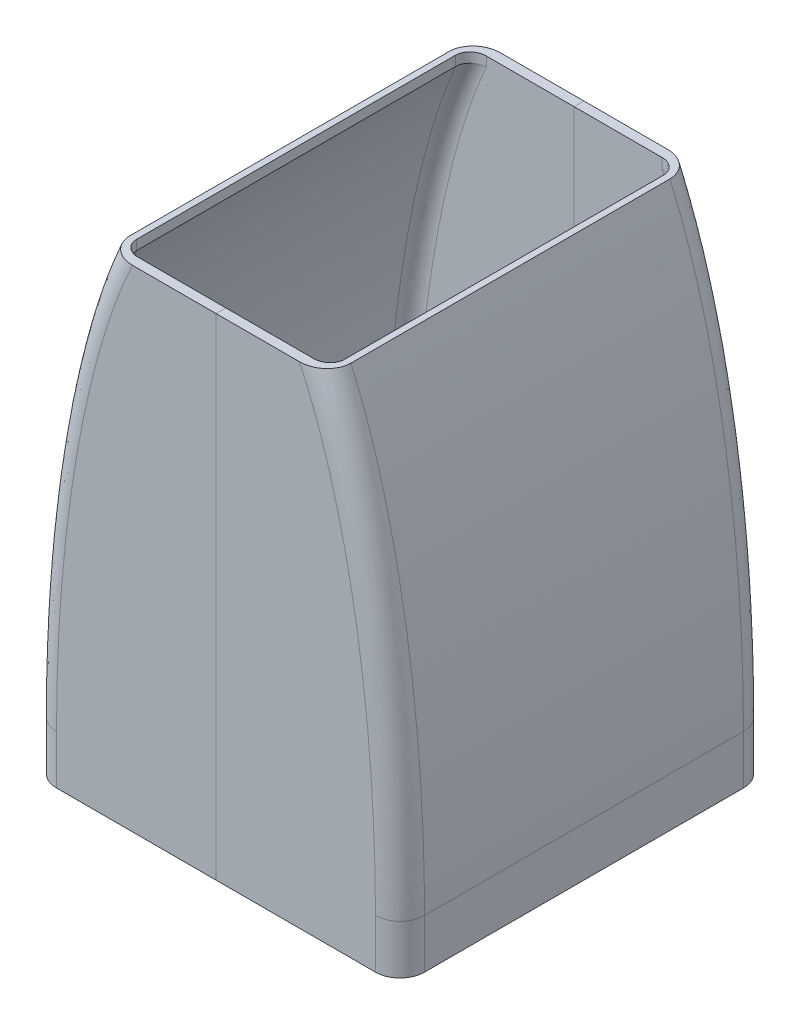
SolidWorks part; units mm, degrees
ref_plane "Front Plane" through (0, 0, 0) normal (0, 0, 1) x (1, 0, 0)
ref_plane "Top Plane" through (0, 0, 0) normal (0, 1, 0) x (1, 0, 0)
ref_plane "Right Plane" through (0, 0, 0) normal (1, 0, 0) x (0, 0, -1)
sketch "Sketch1" plane through (0, 0, 0) normal (0, 1, 0) x (1, 0, 0)
  line L1 (-37.5, 37.5) -> (37.5, 37.5)
  line L2 (-37.5, 37.5) -> (-37.5, -37.5)
  line L3 (-37.5, -37.5) -> (37.5, -37.5)
  line L4 (37.5, 37.5) -> (37.5, -37.5)
  line L5 (-37.5, 37.5) -> (37.5, -37.5) construction
  line L6 (-37.5, -37.5) -> (37.5, 37.5) construction
  point P0 (0, 0)
  dimension "D1" = 75
  dimension "D2" = 75
extrude "Boss-Extrude1" add sketch "Sketch1" along normal blind 10
sketch "Sketch2" plane through (0, 0, 37.5) normal (0, 0, 1) x (1, 0, 0)
  line L0 (0, 0) -> (0, 100) construction
  line L1 (-22.5, 100) -> (22.5, 100)
  line L2 (-37.5, 10) -> (37.5, 10) construction
  line L3 (-37.5, 10) -> (37.5, 10)
  ellipse E0 centre (0, 10) end of major axis (0, 122.5) minor radius 37.5 (-22.5, 100) -> (-37.5, 10) ccw
  ellipse E1 centre (0, 10) end of major axis (0, 122.5) minor radius 37.5 (37.5, 10) -> (22.5, 100) ccw
  point P5 (0, 100)
  dimension "D1" = 100
  dimension "D2" = 45
extrude "Boss-Extrude2" add sketch "Sketch2" against normal blind 75
fillet "Fillet3" radius 5 8 edges at (37.5, 5, 37.5) (33.541, 60.3115, 37.5) (37.5, 5, -37.5) (33.541, 60.3115, -37.5) (-33.541, 60.3115, -37.5) (-37.5, 5, -37.5) (-37.5, 5, 37.5) (-33.541, 60.3115, 37.5)
shell "Shell2" thickness 2 removed face at (0, 0, 0)
sketch "Sketch5" plane through (0, 98, 0) normal (0, -1, 0) x (1, 0, 0)
  line L8 (17.9173, 35.5) -> (-17.9173, 35.5)
  line L9 (-21.1906, 32.5) -> (-21.1906, -32.5)
  line L10 (-17.9173, -35.5) -> (17.9173, -35.5)
  line L11 (21.1906, -32.5) -> (21.1906, 32.5)
  line L12 (17.9173, 35.5) -> (-17.9173, 35.5)
  line L13 (-21.1906, 32.5) -> (-21.1906, -32.5)
  line L14 (-17.9173, -35.5) -> (17.9173, -35.5)
  line L15 (21.1906, -32.5) -> (21.1906, 32.5)
  spline S8 degree 3 poles (652.9657, -3906.7243) (152.9461, -614.5841) (20.8703, 42.3054) (-18.7327, 35.412) (-18.9339, 35.3586) (-19.3197, 35.2184) (-19.505, 35.1318) (-19.8596, 34.9241) (-20.0286, 34.8026) (-20.3362, 34.5325) (-20.4773, 34.3821) (-20.7275, 34.0532) (-20.834, 33.8783) (-21.0089, 33.5075) (-21.0772, 33.3099) (-27.1431, 6.4793) (358.1812, -88.0463) (3904.516, -730.9759) knots -24.254518 -24.254518 -24.254518 -24.254518 0.125 0.125 0.25 0.25 0.375 0.375 0.5 0.5 0.625 0.625 0.75 0.75 0.875 0.875 17.555851 17.555851 17.555851 17.555851 only from (-17.9173, 35.5) to (-21.1906, 32.5)
  spline S9 degree 3 poles (1353.9761, -3785.1154) (108.5431, 47.1093) (-24.7377, -17.2738) (-21.0753, -33.3163) (-21.0082, -33.5093) (-20.8325, -33.8811) (-20.7233, -34.0592) (-20.4755, -34.3839) (-20.3358, -34.533) (-20.0253, -34.8053) (-19.857, -34.9257) (-19.5047, -35.1319) (-19.3194, -35.2187) (16.3833, -48.1691) (182.6697, 533.2285) (-3920.2957, 586.1376) knots -9.764008 -9.764008 -9.764008 -9.764008 0.125 0.125 0.25 0.25 0.375 0.375 0.5 0.5 0.625 0.625 0.75 0.75 23.581318 23.581318 23.581318 23.581318 only from (-21.1906, -32.5) to (-17.9173, -35.5)
  spline S10 degree 3 poles (-652.9657, 3906.7243) (-152.9461, 614.5841) (-20.8703, -42.3054) (18.7327, -35.412) (18.9339, -35.3586) (19.3197, -35.2184) (19.505, -35.1318) (19.8596, -34.9241) (20.0286, -34.8026) (20.3362, -34.5325) (20.4773, -34.3821) (20.7275, -34.0532) (20.834, -33.8783) (21.0089, -33.5075) (21.0772, -33.3099) (27.1431, -6.4793) (-358.1812, 88.0463) (-3904.516, 730.9759) knots -24.254518 -24.254518 -24.254518 -24.254518 0.125 0.125 0.25 0.25 0.375 0.375 0.5 0.5 0.625 0.625 0.75 0.75 0.875 0.875 17.555851 17.555851 17.555851 17.555851 only from (17.9173, -35.5) to (21.1906, -32.5)
  spline S11 degree 3 poles (-1353.9761, 3785.1154) (-108.5431, -47.1093) (24.7377, 17.2738) (21.0753, 33.3163) (21.0082, 33.5093) (20.8325, 33.8811) (20.7233, 34.0592) (20.4755, 34.3839) (20.3358, 34.533) (20.0253, 34.8053) (19.857, 34.9257) (19.5047, 35.1319) (19.3194, 35.2187) (-16.3833, 48.1691) (-182.6697, -533.2285) (3920.2957, -586.1376) knots -9.764008 -9.764008 -9.764008 -9.764008 0.125 0.125 0.25 0.25 0.375 0.375 0.5 0.5 0.625 0.625 0.75 0.75 23.581318 23.581318 23.581318 23.581318 only from (21.1906, 32.5) to (17.9173, 35.5)
  spline S12 degree 3 poles (-17.9173, 35.5) (-18.1242, 35.5) (-18.3287, 35.4823) (-18.7327, 35.412) (-18.9339, 35.3586) (-19.3197, 35.2184) (-19.505, 35.1318) (-19.8596, 34.9241) (-20.0286, 34.8026) (-20.3362, 34.5325) (-20.4773, 34.3821) (-20.7275, 34.0532) (-20.834, 33.8783) (-21.0089, 33.5075) (-21.0772, 33.3099) (-21.1675, 32.9108) (-21.1906, 32.7074) (-21.1906, 32.5) knots 0 0 0 0 0.125 0.125 0.25 0.25 0.375 0.375 0.5 0.5 0.625 0.625 0.75 0.75 0.875 0.875 1 1 1 1
  spline S13 degree 3 poles (-21.1906, -32.5) (-21.1906, -32.7078) (-21.1668, -32.9158) (-21.0753, -33.3163) (-21.0082, -33.5093) (-20.8325, -33.8811) (-20.7233, -34.0592) (-20.4755, -34.3839) (-20.3358, -34.533) (-20.0253, -34.8053) (-19.857, -34.9257) (-19.5047, -35.1319) (-19.3194, -35.2187) (-18.7362, -35.4302) (-18.3317, -35.5) (-17.9173, -35.5) knots 0 0 0 0 0.125 0.125 0.25 0.25 0.375 0.375 0.5 0.5 0.625 0.625 0.75 0.75 1 1 1 1
  spline S14 degree 3 poles (17.9173, -35.5) (18.1242, -35.5) (18.3287, -35.4823) (18.7327, -35.412) (18.9339, -35.3586) (19.3197, -35.2184) (19.505, -35.1318) (19.8596, -34.9241) (20.0286, -34.8026) (20.3362, -34.5325) (20.4773, -34.3821) (20.7275, -34.0532) (20.834, -33.8783) (21.0089, -33.5075) (21.0772, -33.3099) (21.1675, -32.9108) (21.1906, -32.7074) (21.1906, -32.5) knots 0 0 0 0 0.125 0.125 0.25 0.25 0.375 0.375 0.5 0.5 0.625 0.625 0.75 0.75 0.875 0.875 1 1 1 1
  spline S15 degree 3 poles (21.1906, 32.5) (21.1906, 32.7078) (21.1668, 32.9158) (21.0753, 33.3163) (21.0082, 33.5093) (20.8325, 33.8811) (20.7233, 34.0592) (20.4755, 34.3839) (20.3358, 34.533) (20.0253, 34.8053) (19.857, 34.9257) (19.5047, 35.1319) (19.3194, 35.2187) (18.7362, 35.4302) (18.3317, 35.5) (17.9173, 35.5) knots 0 0 0 0 0.125 0.125 0.25 0.25 0.375 0.375 0.5 0.5 0.625 0.625 0.75 0.75 1 1 1 1
  dimension "D1" = 0
extrude "Cut-Extrude3" cut sketch "Sketch5" against normal up to next
split "Split1" trim tools "Right Plane" bodies to split 107 resulting bodies 110 111
